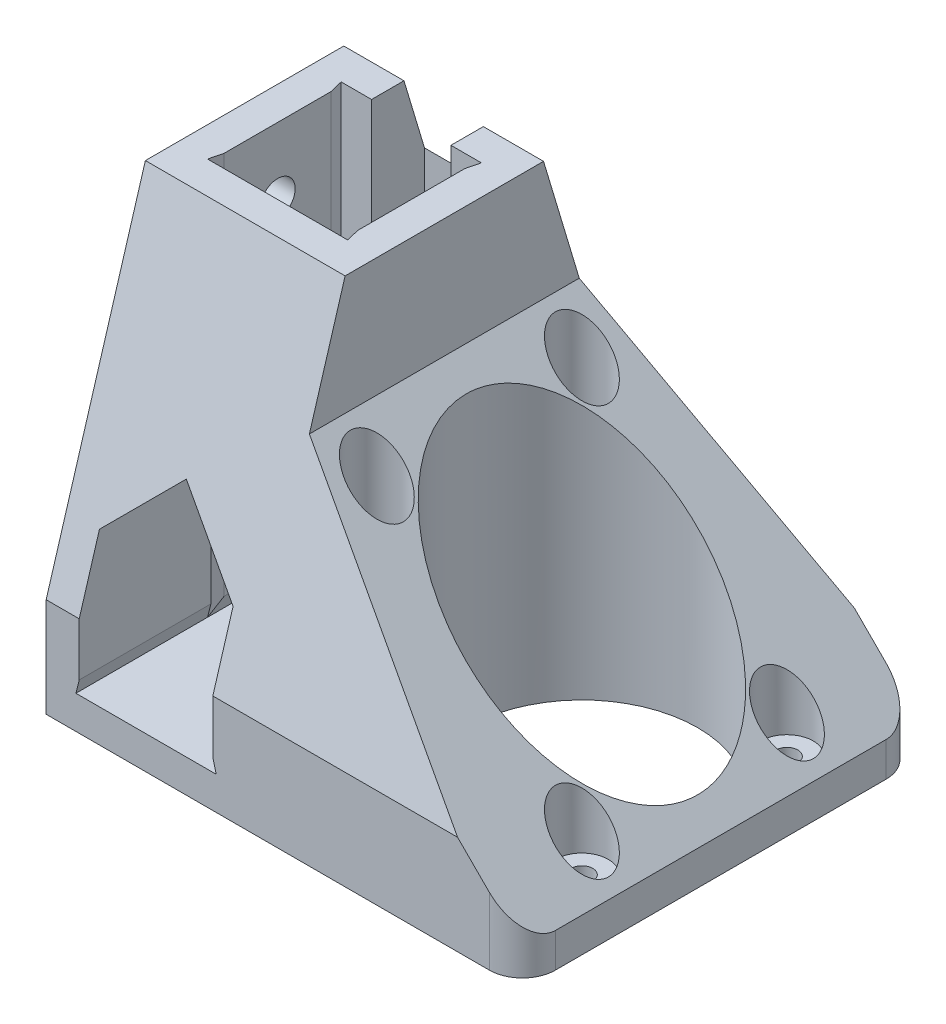
SolidWorks part; units mm, degrees
ref_plane "Front Plane" through (0, 0, 0) normal (0, 0, 1) x (1, 0, 0)
ref_plane "Top Plane" through (0, 0, 0) normal (0, 1, 0) x (1, 0, 0)
ref_plane "Right Plane" through (0, 0, 0) normal (1, 0, 0) x (0, 0, -1)
sketch "Sketch1" plane through (0, 0, 0) normal (0, 1, 0) x (1, 0, 0)
  line L1 (0, 0) -> (72, 0)
  line L2 (0, 0) -> (0, 60)
  line L3 (0, 60) -> (72, 60)
  line L4 (72, 0) -> (72, 60)
  dimension "D1" = 72
  dimension "D2" = 60
extrude "Boss-Extrude1" add sketch "Sketch1" along normal blind 5
sketch "Sketch2" plane through (0, 5, 0) normal (0, 1, 0) x (1, 0, 0)
  line L0 (0, 0) -> (72, 0) construction
  line L1 (0, 60) -> (5, 60)
  line L2 (0, 60) -> (0, 0)
  line L3 (0, 0) -> (5, 0)
  line L4 (5, 60) -> (5, 0)
  dimension "D1" = 5
extrude "Boss-Extrude2" add sketch "Sketch2" along normal blind 60
sketch "Sketch3" plane through (0, 5, 0) normal (0, 1, 0) x (1, 0, 0)
  line L0 (72, 60) -> (5, 60) construction
  line L1 (25.2, 60) -> (30.2, 60)
  line L2 (25.2, 60) -> (25.2, 0)
  line L3 (25.2, 0) -> (30.2, 0)
  line L4 (30.2, 60) -> (30.2, 0)
  line L5 (5, 0) -> (72, 0) construction
  line L6 (5, 0) -> (5, 60) construction
  dimension "D1" = 5
  dimension "D2" = 20.2
extrude "Boss-Extrude3" add sketch "Sketch3" along normal blind 60
sketch "Sketch11" plane through (0, 0, -60) normal (0, 0, -1) x (-1, 0, 0)
  line L0 (-25.2, 25.2) -> (-15.1, 35.3)
  line L1 (-25.2, 65) -> (-25.2, 5) construction
  line L2 (-15.1, 35.3) -> (-5, 25.2)
  line L3 (-5, 65) -> (-5, 5) construction
  line L4 (-5, 25.2) -> (-5, 65)
  line L5 (-5, 65) -> (-25.2, 65)
  line L6 (-25.2, 65) -> (-25.2, 25.2)
  line L7 (-25.2, 5) -> (-5, 5) construction
  dimension "D1" = 20.2
  dimension "D2" = 20.2
  dimension "D3" = 45
  dimension "D4" = 45
extrude "Boss-Extrude4" add sketch "Sketch11" against normal up to surface (60 mm away) up to face at (26.48, 28, 0)
chamfer "Chamfer1" distance 42 angle 45 1 edges at (30.2, 5, -30)
chamfer "Chamfer2" distance 50 angle 16.7 2 edges at (15.1, 65, -60) (15.1, 65, 0) first distance on face at (15.1, 19.14, -60) first distance on face at (15.1, 19.14, 0)
sketch "Sketch12" plane through (0, 65, 0) normal (0, 1, 0) x (1, 0, 0)
  line L0 (0, 30) -> (30.2, 30) construction
  line L1 (5, 40.1) -> (25.2, 40.1)
  line L2 (5, 40.1) -> (5, 19.9)
  line L3 (5, 19.9) -> (25.2, 19.9)
  line L4 (25.2, 40.1) -> (25.2, 19.9)
  line L5 (5, 40.1) -> (25.2, 19.9) construction
  line L6 (5, 19.9) -> (25.2, 40.1) construction
  line L8 (30.2, 9.6005) -> (30.2, 50.3995) construction
  line L9 (0, 44.9993) -> (0, 15.0007) construction
  point P0 (15.1, 30)
  point P8 (15.2, 30)
  point P9 (15.1, 30)
  dimension "D1" = 20.2
  dimension "D2" = 20.2
  dimension "D3" = 5
extrude "Cut-Extrude8" cut sketch "Sketch12" against normal up to surface (60 mm away) up to face at (15.1, 5, -30)
sketch "Sketch5" plane through (0, 5, 0) normal (0, 1, 0) x (1, 0, 0)
  line L0 (72, 0) -> (72, 60) construction
  line L1 (5, 0) -> (25.2, 0) construction
  circle A0 centre (51, 30) radius 17.5
  dimension "D1" = 35
  dimension "D2" = 21
  dimension "D3" = 30
extrude "Cut-Extrude1" cut sketch "Sketch5" against normal through all both and the other way through all
sketch "Sketch6" plane through (0, 0, 0) normal (0, -1, 0) x (1, 0, 0)
  line L1 (35.5, -14.5) -> (66.5, -14.5) construction
  line L2 (35.5, -14.5) -> (35.5, -45.5) construction
  line L3 (35.5, -45.5) -> (66.5, -45.5) construction
  line L4 (66.5, -14.5) -> (66.5, -45.5) construction
  line L5 (35.5, -14.5) -> (66.5, -45.5) construction
  line L6 (35.5, -45.5) -> (66.5, -14.5) construction
  circle A0 centre (66.5, -14.5) radius 1.65
  circle A1 centre (66.5, -45.5) radius 1.65
  circle A2 centre (35.5, -45.5) radius 1.65
  circle A3 centre (35.5, -14.5) radius 1.65
  point P0 (51, -30)
  dimension "D3" = 3.3
  dimension "D1" = 31
  dimension "D2" = 31
extrude "Cut-Extrude2" cut sketch "Sketch6" against normal through all
sketch "Sketch7" plane through (0, 5, 0) normal (0, 1, 0) x (1, 0, 0)
  circle A0 centre (66.5, 45.5) radius 4
  circle A1 centre (66.5, 14.5) radius 4
  circle A2 centre (35.5, 14.5) radius 4
  circle A4 centre (35.5, 45.5) radius 4
  dimension "D1" = 8
extrude "Cut-Extrude4" cut sketch "Sketch7" along normal through all
sketch "Sketch8" plane through (5, 0, 0) normal (1, 0, 0) x (0, 0, -1)
  line L0 (15.0007, 65) -> (44.9993, 65) construction
  line L1 (30, 65) -> (30, 47) construction
  line L2 (9.6005, 47) -> (50.3995, 47) construction
  circle A0 centre (30, 55) radius 2.65
  dimension "D1" = 5.3
  dimension "D2" = 10
extrude "Cut-Extrude5" cut sketch "Sketch8" against normal blind 10
sketch "Sketch9" plane through (0, 0, 0) normal (0, -1, 0) x (1, 0, 0)
  line L1 (0, -60) -> (0, 0) construction
  line L2 (0, -30) -> (72, -30) construction
  line L3 (72, 0) -> (72, -60) construction
  circle A0 centre (15, -30) radius 2.65
  dimension "5.3" = 5.3
  dimension "D2" = 15
extrude "Cut-Extrude6" cut sketch "Sketch9" against normal through all both and the other way through all contours A0
fillet "Fillet1" radius 5 2 edges at (72, 2.6, -60) (72, 2.6, 0)
sketch "Sketch10" plane through (0, 0, 0) normal (-1, 0, 0) x (0, 0, 1)
  line L0 (-60, 0) -> (0, 0) construction
  line L1 (0, 15) -> (0, 0) construction
  circle A0 centre (-30, 15) radius 2.65
  dimension "D3" = 5.3
  dimension "D1" = 15
  dimension "D2" = 30
extrude "Cut-Extrude7" cut sketch "Sketch10" against normal blind 10
sketch "Sketch13" plane through (0, 0, 0) normal (0, 0, 1) x (1, 0, 0)
  line L0 (5, 5) -> (4.5, 5)
  line L1 (4.5, 5) -> (5, 7)
  line L2 (5, 7) -> (5, 5)
  line L3 (25.2, 5) -> (25.7, 5)
  line L4 (25.7, 5) -> (25.2, 7)
  line L5 (25.2, 15) -> (25.2, 5) construction
  line L6 (25.2, 7) -> (25.2, 5)
  dimension "D1" = 2
  dimension "D2" = 2
  dimension "D3" = 0.5
  dimension "D4" = 0.5
extrude "Cut-Extrude9" cut sketch "Sketch13" against normal through all both and the other way through all
sketch "Sketch14" plane through (0, 65, 0) normal (0, 1, 0) x (1, 0, 0)
  line L0 (15.1, 44.9993) -> (15.1, 15.0007) construction
  line L1 (30.2, 44.9993) -> (0, 44.9993) construction
  line L2 (0, 15.0007) -> (30.2, 15.0007) construction
  line L3 (25.2, 40.1) -> (5, 40.1) construction
  line L4 (9.1, 40.1) -> (21.1, 40.1)
  line L5 (9.1, 40.1) -> (9.1, 48.1)
  line L6 (9.1, 48.1) -> (21.1, 48.1)
  line L7 (21.1, 40.1) -> (21.1, 48.1)
  line L8 (15.1, 48.1) -> (15.1, 40.1) construction
  line L14 (25.2, 19.9) -> (25.7, 19.9)
  line L15 (25.7, 19.9) -> (25.2, 21.9)
  line L16 (25.2, 19.9) -> (25.2, 40.1) construction
  line L17 (25.2, 21.9) -> (25.2, 19.9)
  line L18 (5, 19.9) -> (4.5, 19.9)
  line L19 (4.5, 19.9) -> (5, 21.9)
  line L20 (5, 40.1) -> (5, 19.9) construction
  line L21 (5, 21.9) -> (5, 19.9)
  line L22 (25.2, 40.1) -> (25.7, 40.1)
  line L23 (25.7, 40.1) -> (25.2, 38.1)
  line L24 (25.2, 38.1) -> (25.2, 40.1)
  line L25 (5, 40.1) -> (4.5, 40.1)
  line L26 (4.5, 40.1) -> (5, 38.1)
  line L27 (5, 38.1) -> (5, 40.1)
  point P32 (26.2, 38.0272)
  point P34 (25.2, 40.1)
  dimension "D1" = 8
  dimension "D2" = 12
  dimension "D3" = 2
  dimension "D4" = 0.5
  dimension "D5" = 2
  dimension "D6" = 0.5
  dimension "D7" = 2
  dimension "D8" = 0.5
  dimension "D9" = 0.5
  dimension "D10" = 2
extrude "Cut-Extrude10" cut sketch "Sketch14" against normal up to surface (60 mm away) up to face at (15, 5, -32.65)
mirror "Mirror1" [suppressed] of bodies 114
delete or keep bodies "Body-Delete/Keep 1" [suppressed] type delete bodies bodies 114
